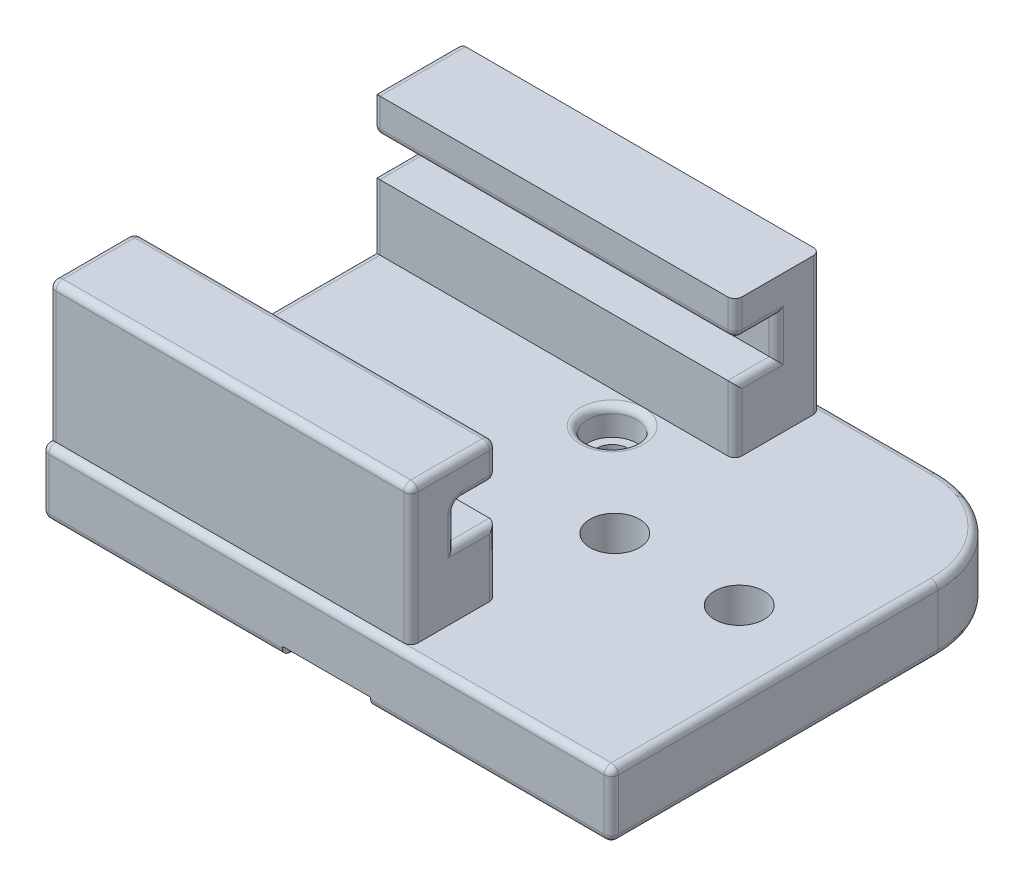
SolidWorks part; units mm, degrees
ref_plane "Front Plane" through (0, 0, 0) normal (0, 0, 1) x (1, 0, 0)
ref_plane "Top Plane" through (0, 0, 0) normal (0, 1, 0) x (1, 0, 0)
ref_plane "Right Plane" through (0, 0, 0) normal (1, 0, 0) x (0, 0, -1)
sketch "Sketch1" plane through (0, 0, 0) normal (0, 1, 0) x (1, 0, 0)
  line L0 (0, -24) -> (0, 24) construction
  line L1 (-32.25, -24) -> (32.25, -24)
  line L2 (-32.25, -24) -> (-32.25, 13)
  line L3 (-21.25, 24) -> (21.25, 24)
  line L4 (32.25, -24) -> (32.25, 13)
  line L5 (-32.25, -24) -> (32.25, 24) construction
  line L6 (-32.25, 24) -> (32.25, -24) construction
  line L7 (-32.25, 13) -> (-32.25, 24)
  line L8 (-32.25, 24) -> (-21.25, 24)
  arc A0 (21.25, 24) -> (32.25, 13) centre (21.25, 13) cw
  circle A2 centre (-20.15, 12.4) radius 5.25
  circle A3 centre (20.25, 12.4) radius 5.25
  circle A4 centre (-1.55, 9.9) radius 1.8
  circle A5 centre (-19.35, -9.7) radius 1.8
  circle A6 centre (23.25, -0.5) radius 2.8
  circle A7 centre (9.15, -0.5) radius 2.8
  point P0 (0, 0)
  dimension "D3" = 11
  dimension "D4" = 10.5
  dimension "D9" = 3.6
  dimension "D13" = 5.6
  dimension "D1" = 64.5
  dimension "D2" = 48
  dimension "D5" = 12.1
  dimension "D6" = 12
  dimension "D7" = 11.6
  dimension "D8" = 30.7
  dimension "D10" = 14.1
  dimension "D11" = 12.9
  dimension "D12" = 14.3
  dimension "D14" = 14.1
  dimension "D15" = 9
  dimension "D16" = 24.5
extrude "Boss-Extrude1" add sketch "Sketch1" along normal blind 7.4
sketch "Sketch3" plane through (0, 7.4, 0) normal (0, 1, 0) x (1, 0, 0)
  circle A0 centre (-19.35, -9.7) radius 2.8
  circle A1 centre (-1.55, 9.9) radius 2.8
  circle A2 centre (9.15, -0.5) radius 2.8
  circle A3 centre (23.25, -0.5) radius 2.8
  circle M11 centre (-19.35, -9.7) radius 1.8
  dimension "D1" = 5.6
  dimension "D2" = 5.6
extrude "Cut-Extrude2" cut sketch "Sketch3" against normal blind 3.1 contours A0 M11 | A1 | A2 | A3 region at (-22.0708, 7.4, 9.7)
ref_plane "Plane1" through (0, 0, 19) normal (0, 0, 1) x (1, 0, 0)
sketch "Sketch7" plane through (0, 7.4, 0) normal (0, 1, 0) x (1, 0, 0)
  circle A0 centre (20.25, 12.4) radius 5.25
  circle A1 centre (-20.15, 12.4) radius 5.25
extrude "Boss-Extrude3" add sketch "Sketch7" against normal blind 3
sketch "Sketch8" plane through (32.25, 0, 0) normal (1, 0, 0) x (0, 0, -1)
  line L1 (0, 16.1396) -> (0, -16.1396) construction
  line L2 (-23.2, 7.4) -> (-18.2, 7.4)
  line L3 (-24, 7.4) -> (13, 7.4) construction
  line L4 (-18.2, 7.4) -> (-18.2, 19)
  line L5 (-18.2, 19) -> (-13.5, 19)
  line L6 (-13.5, 19) -> (-13.5, 23)
  line L7 (-13.5, 23) -> (-23.2, 23)
  line L8 (-23.2, 23) -> (-23.2, 7.4)
  line L9 (13.5, 23) -> (23.2, 23)
  line L10 (13.5, 19) -> (13.5, 23)
  line L11 (18.2, 19) -> (13.5, 19)
  line L12 (18.2, 7.4) -> (18.2, 19)
  line L13 (23.2, 7.4) -> (18.2, 7.4)
  line L14 (23.2, 23) -> (23.2, 7.4)
  point P0 (0, 0)
  dimension "D1" = 13.5
  dimension "D2" = 5
  dimension "D3" = 15.6
  dimension "D4" = 18.2
  dimension "D5" = 4
extrude "Boss-Extrude4" add sketch "Sketch8" against normal blind 41 from offset 23.5 offset against normal yes
sketch "Sketch11" plane through (0, 0, 0) normal (1, 0, 0) x (0, 0, -1)
  line L0 (0, 3.6102) -> (0, 11.4741)
  line L1 (-18.2, 7.4) -> (-13.5, 7.4)
  line L2 (-18.2, 7.4) -> (-18.2, 14.8)
  line L3 (-18.2, 14.8) -> (-13.5, 14.8)
  line L4 (-13.5, 7.4) -> (-13.5, 14.8)
  line L6 (18.2, 14.8) -> (13.5, 14.8)
  line L7 (13.5, 7.4) -> (13.5, 14.8)
  line L8 (18.2, 7.4) -> (13.5, 7.4)
  line L9 (18.2, 7.4) -> (18.2, 14.8)
  dimension "D1" = 7.4
  dimension "D2" = 4.7
extrude "Boss-Extrude6" add sketch "Sketch11" against normal blind 41 from offset 8.75 contours L1 L4 L3 L2 | L8 L9 L6 L7 region at (0, 11.1, 15.85) region at (0, 11.1, -15.85)
fillet "Fillet1" radius 0.8 49 edges at (32.25, 7.4, 5.5) (29.0282, 7.4, -20.7782) (32.25, 0, 5.5) (29.0282, 0, -20.7782) (0, 7.4, 24) (32.25, 3.7, 24) (0, 0, 24) (-5.5, 7.4, -24) (-5.5, 0, -24) (-32.25, 7.4, 23.6) (-32.25, 3.7, 24) (-32.25, 0, 0) (-11.75, 23, 23.2) (-11.75, 23, 13.5) (8.75, 23, 18.35) (-11.75, 19, 18.2) (8.75, 16.9, 18.2) (8.75, 19, 15.85) (8.75, 19, -15.85) (8.75, 15.2, 23.2) (8.75, 15.2, -23.2) (-11.75, 19, 13.5) (-11.75, 19, -13.5) (-1.55, 7.4, -7.1) (-19.35, 7.4, 12.5) (8.75, 21, -13.5) (8.75, 21, 13.5) (-32.25, 3.7, -24) (-32.25, 7.4, -23.6) (-32.25, 15.2, -23.2) (-32.25, 23, -18.35) (-32.25, 21, -13.5) (-32.25, 19, -15.85) (-32.25, 16.9, -18.2) (-32.25, 16.9, 18.2) (-32.25, 19, 15.85) (-32.25, 21, 13.5) (-32.25, 15.2, 23.2) (-32.25, 23, 18.35) (-32.25, 11.1, 13.5) (-32.25, 14.8, 15.85) (-32.25, 14.8, -15.85) (-32.25, 11.1, -13.5) (-32.25, 7.4, 0) (8.75, 16.9, -18.2) (8.75, 14.8, -15.85) (8.75, 11.1, -13.5) (8.75, 11.1, 13.5) (8.75, 14.8, 15.85)
sketch "Sketch10" plane through (0, 0, 0) normal (0, -1, 0) x (1, 0, 0)
  line L1 (31.45, 23.2) -> (-31.45, 23.2) construction
  line L3 (-31.45, 24) -> (31.45, 24) construction
  line L4 (-5, 23.2) -> (-5, 24)
  line L5 (-5, 24) -> (5, 24)
  line L6 (5, 23.2) -> (5, 24)
  arc A0 (-5, 23.2) -> (5, 23.2) centre (0, 24.4907) ccw
  point P7 (0, 23.2)
  point P12 (0, 23.9741)
  dimension "D2" = 10
extrude "Cut-Extrude3" cut sketch "Sketch10" against normal blind 1
fillet "Fillet2" radius 1 2 edges at (9.15, 0, 3.3) (23.25, 0, 3.3)
